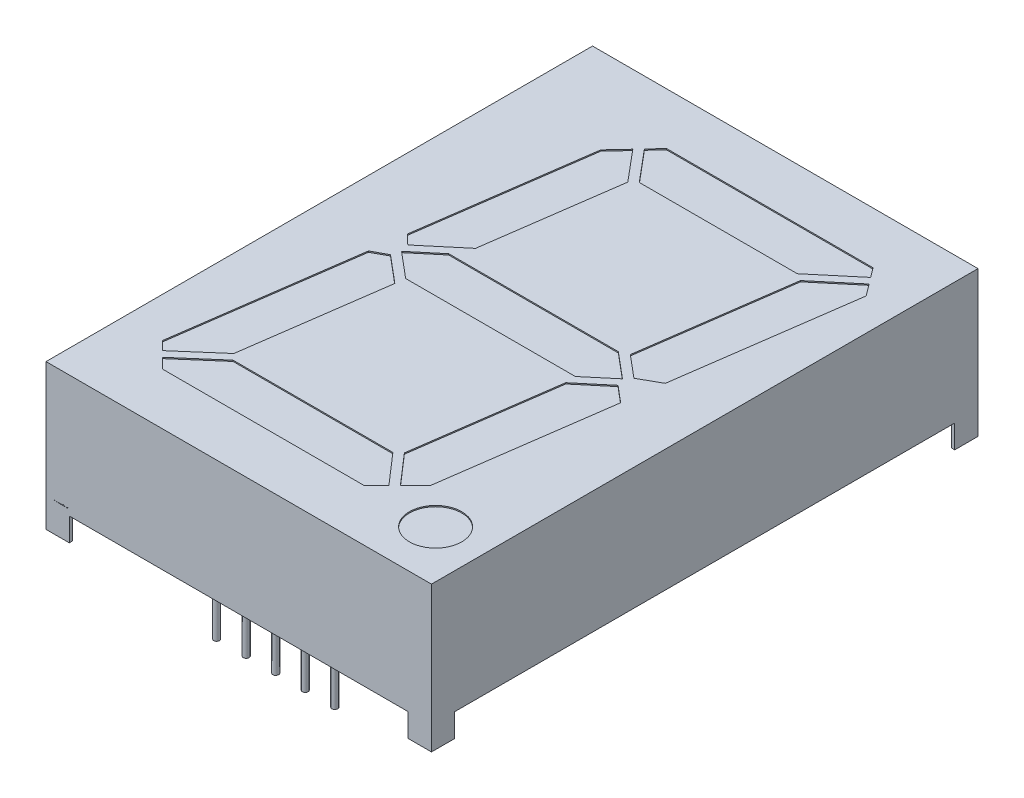
SolidWorks part; units mm, degrees
note: The reader was unsure of these and kept them because the rebuilt part matched: shared geometry of "Sketch7<3>", "Sketch7<4>".
ref_plane "Front Plane" through (0, 0, 0) normal (0, 0, 1) x (1, 0, 0)
ref_plane "Top Plane" through (0, 0, 0) normal (0, 1, 0) x (1, 0, 0)
ref_plane "Right Plane" through (0, 0, 0) normal (1, 0, 0) x (0, 0, -1)
sketch "Sketch1" plane through (0, 0, 0) normal (0, 1, 0) x (1, 0, 0)
  line L0 (-16.575, 23.5) -> (16.575, -23.5) construction
  line L1 (-16.575, 23.5) -> (16.575, 23.5)
  line L2 (-16.575, 23.5) -> (-16.575, -23.5)
  line L3 (-16.575, -23.5) -> (16.575, -23.5)
  line L4 (16.575, 23.5) -> (16.575, -23.5)
  dimension "D1" = 33.15
  dimension "D2" = 47
extrude "Extrude2" add sketch "Sketch1" against normal blind 12.5
sketch "Sketch2" plane through (0, 0, 23.5) normal (0, 0, 1) x (1, 0, 0)
  line L0 (-14.575, -12.5) -> (-14.575, -10.5)
  line L1 (-16.575, -12.5) -> (16.575, -12.5) construction
  line L2 (-14.575, -10.5) -> (14.575, -10.5)
  line L3 (14.575, -10.5) -> (14.575, -12.5)
  line L4 (-14.575, -12.5) -> (14.575, -12.5)
  line L5 (0, -10.5) -> (0, -12.5) construction
  line M3 (-16.575, -12.5) -> (16.575, -12.5)
  dimension "D1" = 2
  dimension "D2" = 2
extrude "Cut-Extrude2" cut sketch "Sketch2" against normal through all contours L5 L2 L0 M3 | L5 L3 L2 M3
sketch "Sketch3" plane through (16.575, 0, 0) normal (1, 0, 0) x (0, 0, -1)
  line L0 (-21.5, -12.5) -> (-21.5, -10.5)
  line L2 (-21.5, -10.5) -> (21.5, -10.5)
  line L3 (21.5, -10.5) -> (21.5, -12.5)
  line L4 (21.5, -12.5) -> (-21.5, -12.5)
  line L6 (0, 0) -> (0, -12.5) construction
  line L7 (23.5, -12.5) -> (-23.5, -12.5) construction
  line L11 (0, -10.5) -> (0, -12.5) construction
  dimension "D1" = 2
  dimension "D2" = 2
extrude "Cut-Extrude3" cut sketch "Sketch3" against normal through all
sketch "Sketch6" plane through (0, 0, 0) normal (0, 1, 0) x (-1, 0, 0)
  line L0 (8.0753, -19.05) -> (13.4299, 19.05)
  line L1 (13.4299, 19.05) -> (-8.7863, 19.05)
  line L2 (-8.7863, 19.05) -> (-14.1409, -19.05)
  line L3 (-14.1409, -19.05) -> (8.0753, -19.05)
  line L4 (-3.8912, 0) -> (5.5533, 0) construction
  line L5 (8.1248, -18.6976) -> (4.9245, -14.8836)
  line L6 (-11.4636, 0) -> (-3.8912, 0) construction
  line L7 (-7.3425, 16.8556) -> (-12.0014, -16.7978) construction
  line L8 (-3.0328, -19.05) -> (-3.0328, 0) construction
  line L9 (9.1735, 15.35) -> (-5.57, 15.35)
  line L10 (4.8589, -15.35) -> (9.1735, 15.35)
  line L11 (-9.8846, -15.35) -> (4.8589, -15.35)
  line L12 (-5.57, 15.35) -> (-9.8846, -15.35)
  line L13 (7.5886, -19.1476) -> (4.3882, -15.3336)
  line L14 (-5.1062, 15.35) -> (-8.5222, 19.2796)
  line L15 (-5.6345, 14.8908) -> (-9.0505, 18.8204)
  line L16 (-14.3659, -18.7819) -> (-9.6369, -14.8138)
  line L17 (-13.916, -19.3181) -> (-9.1869, -15.35)
  line L18 (8.64, 15.35) -> (13.2003, 19.3141)
  line L19 (9.0993, 14.8217) -> (13.6595, 18.7859)
  line L20 (-8.0291, -2.148) -> (-9.947, -0.5387)
  line L21 (-9.947, -0.5387) -> (-11.6756, -1.5086)
  line L22 (7.2953, -1.85) -> (9.5, 0)
  line L23 (-9.5, 0) -> (-7.2953, 1.85)
  line L24 (7.2953, 1.85) -> (-7.2953, 1.85)
  line L25 (7.2953, 1.85) -> (9.5, 0)
  line L26 (-9.5, 0) -> (-7.2953, -1.85)
  line L27 (7.2953, -1.85) -> (-7.2953, -1.85)
  line L28 (6.5386, -3.3987) -> (9.7043, -0.7424)
  line L29 (9.7043, -0.7424) -> (10.5368, -1.5356)
  line L30 (10.9486, 1.3947) -> (9.7265, 0.7237)
  line L31 (9.7265, 0.7237) -> (7.3931, 2.6817)
  line L32 (0, -1.85) -> (0, 1.85) construction
  line L33 (-3.0328, -19.05) -> (0, -1.85) construction
  line L34 (0, 0) -> (-3.0328, 0) construction
  line L38 (-9.1869, -15.35) -> (-9.6369, -14.8138)
  line L39 (-7.3447, 2.7223) -> (-9.7898, 0.6706)
  line L40 (-9.7898, 0.6706) -> (-11.2022, 1.8603)
  line L42 (-13.916, -19.3181) -> (-14.3659, -18.7819)
  line L43 (-9.4119, -15.0819) -> (-14.1409, -19.05) construction
  line L44 (7.5886, -19.1476) -> (8.1248, -18.6976)
  line L45 (4.3882, -15.3336) -> (4.9245, -14.8836)
  line L46 (7.8567, -18.9226) -> (4.6563, -15.1086) construction
  line L47 (9.0993, 14.8217) -> (8.64, 15.35) construction
  line L48 (13.6595, 18.7859) -> (13.2003, 19.3141) construction
  line L49 (13.4299, 19.05) -> (8.8697, 15.0859) construction
  line L50 (-5.1062, 15.35) -> (-5.6345, 14.8908)
  line L51 (-8.5222, 19.2796) -> (-9.0505, 18.8204)
  line L52 (-5.3704, 15.1204) -> (-8.7863, 19.05) construction
  line L53 (8.4864, -16.1246) -> (5.7584, -19.05)
  line L54 (-11.9988, -19.05) -> (-13.8042, -16.6541)
  line L55 (13.1318, 16.9287) -> (11.0104, 19.05)
  line L56 (-6.3554, 19.05) -> (-9.1838, 16.2216)
  line L57 (2.3218, 19.05) -> (-16.575, 19.05) construction
  line L58 (-16.575, -23.5) -> (-16.575, 23.5) construction
  circle A0 centre (-12.4802, 19.05) radius 2.25
  dimension "D32" = 4.5
  dimension "D1" = 22
  dimension "D2" = 38.1
  dimension "D3" = 8
  dimension "D6" = 130
  dimension "D8" = 140
  dimension "D9" = 0.7
  dimension "D10" = 0.7
  dimension "D11" = 0.7
  dimension "D12" = 80
  dimension "D13" = 10
  dimension "D14" = 3.7
  dimension "D15" = 0.7
  dimension "D17" = 19
  dimension "D22" = 0.7
  dimension "D23" = 0.7
  dimension "D24" = 35
  dimension "D25" = 3
  dimension "D26" = 45
  dimension "D27" = 45
  dimension "D28" = 3
  dimension "D29" = 4
  dimension "D30" = 45
  dimension "D31" = 4
  dimension "D4" = 3.7
  dimension "D5" = 0.7
  dimension "D7" = 0.7
extrude "Cut-Extrude4" cut sketch "Sketch6" against normal blind 0.1
sketch "Sketch7" plane through (0, -12.5, 0) normal (0, -1, 0) x (1, 0, 0)
  line L0 (0, 0) -> (16.575, 0) construction
  line L1 (16.575, 21.5) -> (16.575, -21.5) construction
  line L2 (-16.575, 21.5) -> (-16.575, -21.5) construction
  line L3 (-16.275, 23.2) -> (-14.575, 23.2)
  line L4 (-16.275, 23.2) -> (-16.275, 21.5)
  line L5 (-16.275, 21.5) -> (-14.575, 21.5)
  line L6 (-14.575, 23.2) -> (-14.575, 21.5)
  line L7 (-16.575, 23.5) -> (-14.575, 23.5) construction
  line L8 (-14.575, 21.5) -> (-14.575, 23.5) construction
  line L9 (-16.575, 21.5) -> (-14.575, 21.5) construction
  line L10 (-14.575, -23.2) -> (-14.575, -21.5)
  line L11 (-16.275, -21.5) -> (-14.575, -21.5)
  line L12 (-16.275, -23.2) -> (-16.275, -21.5)
  line L13 (-16.275, -23.2) -> (-14.575, -23.2)
  line L14 (0, 0) -> (0, -23.5) construction
  line L15 (-14.575, -23.5) -> (14.575, -23.5) construction
  line L16 (16.275, -23.2) -> (14.575, -23.2)
  line L17 (16.275, -23.2) -> (16.275, -21.5)
  line L18 (16.275, -21.5) -> (14.575, -21.5)
  line L19 (14.575, -23.2) -> (14.575, -21.5)
  line L20 (14.575, 23.2) -> (14.575, 21.5)
  line L21 (16.275, 21.5) -> (14.575, 21.5)
  line L22 (16.275, 23.2) -> (16.275, 21.5)
  line L23 (16.275, 23.2) -> (14.575, 23.2)
  circle A0 centre (-5.08, 20.32) radius 0.25
  circle A1 centre (-2.54, 20.32) radius 0.25
  circle A2 centre (0, 20.32) radius 0.25
  circle A3 centre (5.08, 20.32) radius 0.25
  circle A4 centre (2.54, 20.32) radius 0.25
  circle A5 centre (2.54, -20.32) radius 0.25
  circle A6 centre (5.08, -20.32) radius 0.25
  circle A7 centre (0, -20.32) radius 0.25
  circle A8 centre (-2.54, -20.32) radius 0.25
  circle A9 centre (-5.08, -20.32) radius 0.25
  dimension "D1" = 0.5
  dimension "D2" = 2.54
  dimension "D3" = 2.54
  dimension "D4" = 2.54
  dimension "D5" = 2.54
  dimension "D6" = 40.64
  dimension "D7" = 0.3
  dimension "D8" = 0.3
extrude "Cut-Extrude6" cut sketch "Sketch7" against normal up to surface (2 mm away) contours L5 L6 L3 L4 | L10 L11 L12 L13 | L16 L19 L18 L17 | L21 L20 L23 L22 up to face at (0, -10.5, 0)
extrude "Extrude3" add sketch "Sketch7<3>" against normal up to surface (2 mm away)
sketch "Sketch7<3>" plane through (0, -12.5, 0) normal (0, -1, 0) x (1, 0, 0) same geometry as "Sketch7"
extrude "Extrude4" add sketch "Sketch7<4>" along normal blind 4
sketch "Sketch7<4>" plane through (0, -12.5, 0) normal (0, -1, 0) x (1, 0, 0) same geometry as "Sketch7"
sketch "Sketch8" plane through (0, 0, 23.5) normal (0, 0, 1) x (1, 0, 0)
  line L0 (-16.575, -10) -> (-14.075, -10) construction
  line L1 (-16.575, -12.5) -> (-16.575, 0) construction
  line L2 (-16.575, -12.5) -> (-14.575, -12.5) construction
  text T0 "www.KingbrightUSA.com" font "Century Gothic" height 0.08
  dimension "D1" = 2.5
  dimension "D2" = 2.5
extrude "Cut-Extrude7" cut sketch "Sketch8" against normal blind 0.01
